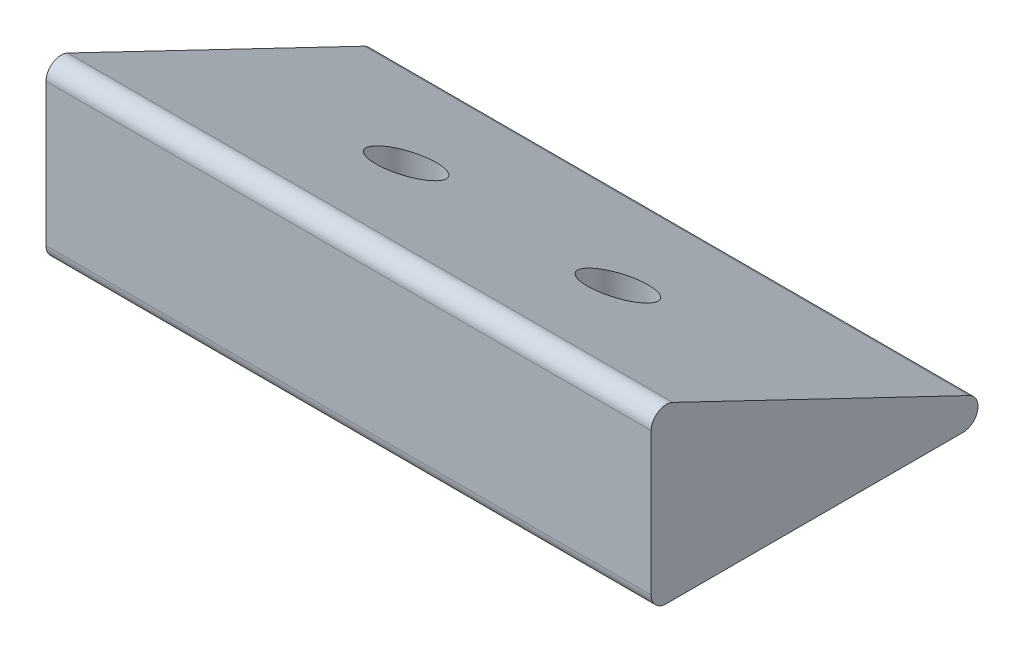
SolidWorks part; units mm, degrees
material "Rubber"
ref_plane "Front Plane" through (0, 0, 0) normal (0, 0, 1) x (1, 0, 0)
ref_plane "Top Plane" through (0, 0, 0) normal (0, 1, 0) x (1, 0, 0)
ref_plane "Right Plane" through (0, 0, 0) normal (1, 0, 0) x (0, 0, -1)
sketch "Sketch1" plane through (0, 0, 0) normal (1, 0, 0) x (0, 0, -1)
  line L0 (2, 0) -> (20.6058, 0)
  line L1 (21.0385, 1.9015) -> (2.8655, 10.6246)
  line L2 (0, 8.8215) -> (0, 2)
  arc A0 (0, 8.8215) -> (2.8655, 10.6246) centre (2, 8.8215) cw
  arc A1 (2, 0) -> (0, 2) centre (2, 2) cw
  arc A2 (21.0385, 1.9015) -> (20.6058, 0) centre (20.6058, 1) cw
  point P6 (0, 12)
  point P9 (0, 0)
  point P12 (25, 0)
  dimension "D1" = 12
  dimension "D3" = 2
  dimension "D4" = 1
  dimension "D2" = 25
extrude "Boss-Extrude1" [suppressed] add sketch "Sketch1" along normal blind 99
ref_plane "Plane1" [suppressed] through (0, 10, 0) normal (0, 1, 0) x (1, 0, 0)
sketch "Sketch2" [suppressed] plane through (0, 10, 0) normal (0, 1, 0) x (1, 0, 0)
  line L0 (99, 11.952) -> (0, 11.952) construction
  line L1 (99, 21.0385) -> (99, 2.8655) construction
  line L2 (0, 21.0385) -> (0, 2.8655) construction
  line L3 (49.5, 11.952) -> (49.5, 18.9766) construction
  circle A0 centre (42.5, 11.952) radius 2
  circle A1 centre (56.5, 11.952) radius 2
  dimension "D1" = 4
  dimension "D2" = 7
extrude "Cut-Extrude1" [suppressed] cut sketch "Sketch2" against normal blind 8
sketch "Sketch3" [suppressed] plane through (0, 2, 0) normal (0, 1, 0) x (1, 0, 0)
  circle A0 centre (42.5, 11.952) radius 1.5
  circle A1 centre (56.5, 11.952) radius 1.5
  dimension "D1" = 3
extrude "Cut-Extrude2" [suppressed] cut sketch "Sketch3" against normal through all
sketch "Sketch4" plane through (0, 0, 0) normal (1, 0, 0) x (0, 0, -1)
  line L0 (0, 1) -> (0, 10.4108)
  line L1 (1.4327, 11.3123) -> (21.0385, 1.9015)
  line L2 (20.6058, 0) -> (1, 0)
  arc A0 (20.6058, 0) -> (21.0385, 1.9015) centre (20.6058, 1) ccw
  arc A1 (1, 0) -> (0, 1) centre (1, 1) cw
  arc A2 (1.4327, 11.3123) -> (0, 10.4108) centre (1, 10.4108) ccw
  point P6 (25, 0)
  point P9 (0, 0)
  point P12 (0, 12)
  dimension "D3" = 1
  dimension "D1" = 25
  dimension "D2" = 12
extrude "Boss-Extrude2" add sketch "Sketch4" along normal blind 40
ref_plane "Plane2" through (0, 10, 0) normal (0, -1, 0) x (-1, 0, 0)
sketch "Sketch5" plane through (0, 10, 0) normal (0, -1, 0) x (-1, 0, 0)
  line L0 (-20, 0) -> (-20, 21.6058) construction
  line L1 (-40, 0) -> (0, 0) construction
  line L2 (0, 21.6058) -> (-40, 21.6058) construction
  line L3 (-20, 10.8029) -> (-13, 10.8029) construction
  circle A0 centre (-13, 10.8029) radius 2
  circle A1 centre (-27, 10.8029) radius 2
  dimension "D1" = 4
  dimension "D2" = 14
extrude "Cut-Extrude4" cut sketch "Sketch5" along normal blind 8
sketch "Sketch6" plane through (0, 2, 0) normal (0, 1, 0) x (1, 0, 0)
  circle A0 centre (13, 10.8029) radius 1.5
  circle A1 centre (27, 10.8029) radius 1.5
  dimension "D1" = 3
extrude "Cut-Extrude5" cut sketch "Sketch6" against normal blind 8
